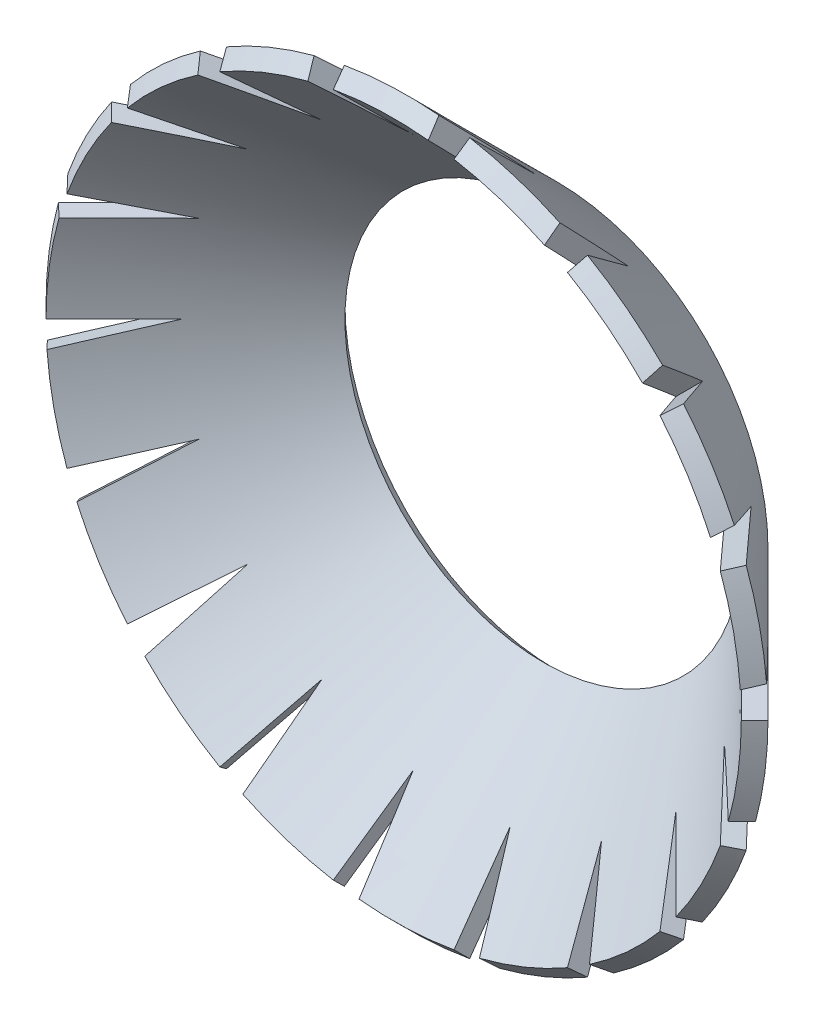
SolidWorks part; units mm, degrees
ref_plane "Front Plane" through (0, 0, 0) normal (0, 0, 1) x (1, 0, 0)
ref_plane "Top Plane" through (0, 0, 0) normal (0, 1, 0) x (1, 0, 0)
ref_plane "Right Plane" through (0, 0, 0) normal (1, 0, 0) x (0, 0, -1)
sketch "BodySke" plane through (0, 0, 0) normal (0, 1, 0) x (1, 0, 0)
  line L0 (0, -1.6) -> (0, 3.997) construction
  line L1 (0, 0) -> (7.65, 0) construction
  line L2 (7.65, 0) -> (5.2387, 2.4113) construction
  line L3 (7.65, 0) -> (4.4828, 3.1672)
  line L4 (7.65, 0) -> (7.3672, -0.2828)
  line L5 (7.3672, -0.2828) -> (4.2, 2.8843)
  line L6 (4.2, 2.8843) -> (4.4828, 3.1672)
  line L7 (0, 0) -> (-18, 0) construction
  dimension "Inner_dia" = 8.4
revolve "BaseBody" add sketch "BodySke" angle 360 about L0
sketch "ToothSke" plane through (0, 0, 0) normal (0, 0, 1) x (1, 0, 0)
  line L0 (0, 0) -> (4.8783, 0) construction
  line L1 (7.65, 0) -> (7.65, 0.6676)
  line L2 (7.65, -0.6676) -> (7.65, 0.6676) construction
  line L4 (5.925, 0) -> (7.65, 0.6676)
  line L5 (5.925, 0) -> (7.65, 0)
  circle A0 centre (0, 0) radius 7.65 construction
  circle A1 centre (0, 0) radius 7.65 construction
  arc A2 (-5.925, 0) -> (5.9026, 0.5147) centre (0, 0) ccw construction
  point P9 (7.65, 0)
  dimension "D1" = 11.85
  dimension "D2" = 1.3352
extrude "ToothCut" cut sketch "ToothSke" against normal through all and the other way through all
pattern_circular "ToothPat" count 18 over 360 about axis through (0, 0, 1.6) along (0, 0, -1) of "ToothCut"
equation "\"D1@ToothSke\" =  ( \"Outer_dia@BodySke\" + \"Inner_dia@BodySke\" )  / 2"
equation "\"D2@ToothSke\" = pi  * \"Outer_dia@BodySke\" / 2 / \"Num_tooth@BodySke\""
equation "\"Num_tooth@ToothPat\" = \"Num_tooth@BodySke\""
